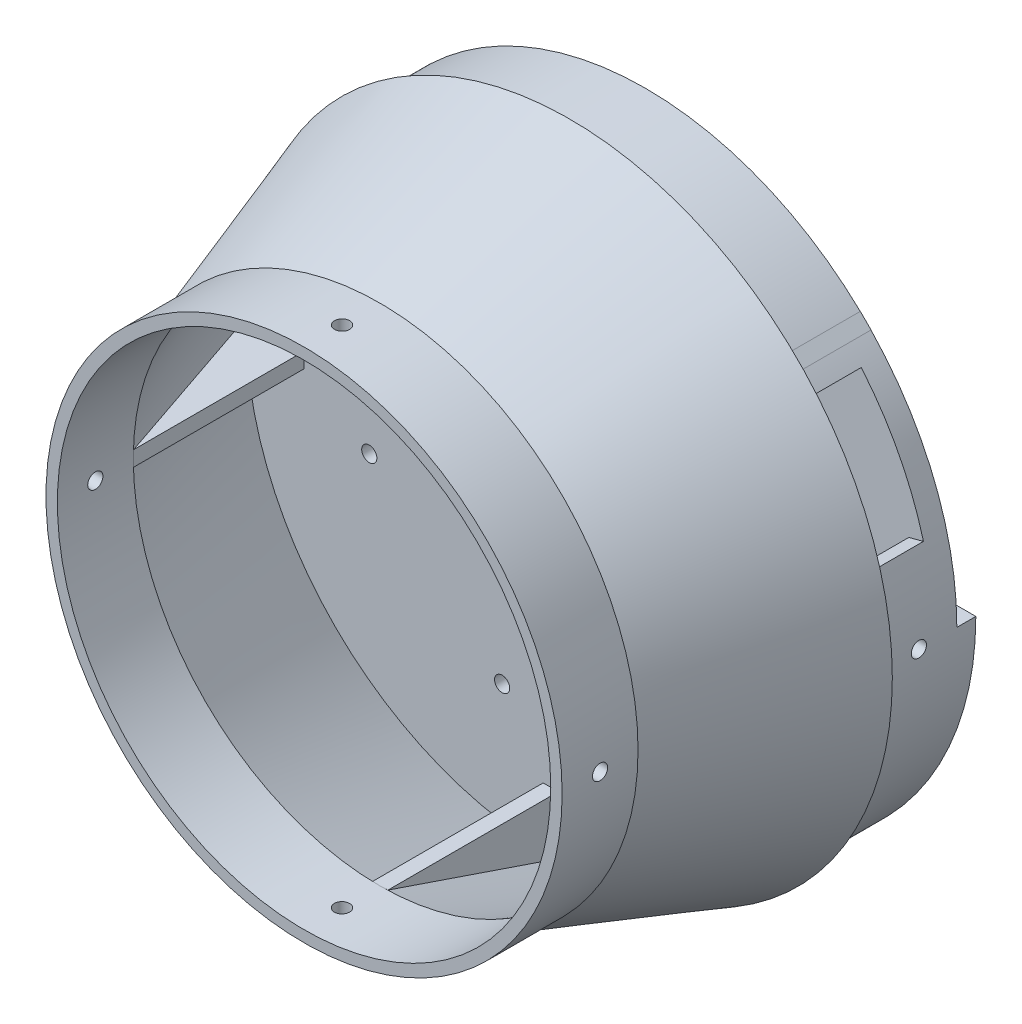
SolidWorks part; units mm, degrees
material "Polyetheretherketone (PEEK)"
ref_plane "Front Plane" through (0, 0, 0) normal (0, 0, 1) x (1, 0, 0)
ref_plane "Top Plane" through (0, 0, 0) normal (0, 1, 0) x (1, 0, 0)
ref_plane "Right Plane" through (0, 0, 0) normal (1, 0, 0) x (0, 0, -1)
sketch "Sketch10" plane through (0, 0, 0) normal (0, 1, 0) x (1, 0, 0)
  line L9 (68, 0) -> (85, 50)
  line L10 (65, 0) -> (65, -20)
  line L11 (65, -20) -> (68, -20)
  line L12 (68, -20) -> (68, 0)
  line L13 (85, 50) -> (0, 50)
  line L14 (0, 50) -> (0, 45)
  line L16 (0, 0) -> (0, 90.5218) construction
  line L17 (65, 0) -> (80.3, 45)
  line L18 (0, 45) -> (80.3, 45)
  dimension "D1" = 65
  dimension "D2" = 20
  dimension "D3" = 50
  dimension "D4" = 85
  dimension "D5" = 68
  dimension "D6" = 5
revolve "Revolve2" add sketch "Sketch10" angle 360 about L16
sketch "Sketch12" plane through (0, 0, 0) normal (0, 1, 0) x (1, 0, 0)
  line L4 (-80.3, 45) -> (-65, 0)
  line L5 (-65, 0) -> (-65, 45)
  line L6 (-80.3, 45) -> (80.3, 45) construction
  line L7 (-65, 45) -> (-80.3, 45)
extrude "Boss-Extrude5" add sketch "Sketch12" along normal blind 2 and the other way blind 2
pattern_circular "CirPattern3" count 4 every 90 about axis through (0, 0, -50) along (0, 0, 1) of "Boss-Extrude5"
sketch "Sketch13" plane through (0, 0, -50) normal (0, 0, -1) x (-1, 0, 0)
  arc A0 (70, 42.7083) -> (70, -42.7083) centre (0, 0) ccw
  arc A1 (70, 34.4093) -> (70, -34.4093) centre (0, 0) ccw
  circle A2 centre (0, 0) radius 82 construction
  circle A3 centre (0, 0) radius 78 construction
  circle A4 centre (0, 0) radius 82
  circle A5 centre (0, 0) radius 78
  dimension "D1" = 164
  dimension "D2" = 4
extrude "Boss-Extrude6" add sketch "Sketch13" along normal blind 20 contours A0 A4 A5 A1 region at (-76.7102, 21.5537, -50)
sketch "Sketch14" plane through (0, 0, 0) normal (0, 1, 0) x (1, 0, 0)
  line L0 (-65, -20) -> (65, -20) construction
  circle A0 centre (0, -10) radius 2
  dimension "D1" = 4
  dimension "D2" = 10
extrude "Cut-Extrude1" cut sketch "Sketch14" against normal blind 95
pattern_circular "CirPattern4" count 4 every 90 about axis through (0, 0, 20) along (0, 0, 1) of "Cut-Extrude1"
sketch "Sketch16" plane through (0, 0, 0) normal (0, 1, 0) x (1, 0, 0)
  line L0 (85, 50) -> (-85, 50) construction
  circle A0 centre (0, 60) radius 2
  dimension "D1" = 4
  dimension "D2" = 10
extrude "Cut-Extrude2" cut sketch "Sketch16" against normal blind 94
pattern_circular "CirPattern5" count 2 every 90 about axis through (0, 0, -70) along (0, 0, -1) of "Cut-Extrude2" other way count 2
sketch "Sketch17" plane through (0, 0, -50) normal (0, 0, -1) x (-1, 0, 0)
  line L0 (0, 0) -> (-47.8133, 12.8115) construction
  line L1 (0, 0) -> (-12.8115, 47.8133) construction
  circle A0 centre (-47.8133, 12.8115) radius 2
  circle A4 centre (-12.8115, 47.8133) radius 2
  circle A5 centre (12.8115, -47.8133) radius 2
  circle A6 centre (47.8133, -12.8115) radius 2
  point P12 (0, 0)
  point P16 (0, 0)
  dimension "D1" = 4
  dimension "D2" = 49.5
  dimension "D4" = 60
  dimension "D3" = 2
  dimension "D5" = 2
extrude "Cut-Extrude4" cut sketch "Sketch17" against normal blind 900
sketch "Sketch19" plane through (0, 0, -70) normal (0, 0, -1) x (-1, 0, 0)
  line L0 (0, 0) -> (0, 85) construction
  line L1 (0, 0) -> (-79.2059, 21.2232)
  line L6 (0, 0) -> (-62.8156, 52.7086)
  circle A0 centre (0, 0) radius 85 construction
  arc A2 (-62.8156, 52.7086) -> (-79.2059, 21.2232) centre (0, 0) ccw
  dimension "D1" = 75
  dimension "D2" = 50
extrude "Cut-Extrude7" cut sketch "Sketch19" against normal blind 20
mirror "Mirror1" about plane through (0, 0, 0) normal (1, 0, 0) of "Cut-Extrude7"
sketch "Sketch22" plane through (0, 0, -70) normal (0, 0, -1) x (-1, 0, 0)
  circle A2 centre (0, 0) radius 82
  circle A3 centre (0, 0) radius 60
  arc M2 (-59.7515, 50.1374) -> (59.7515, 50.1374) centre (0, 0) cw
  line M3 (59.7515, 50.1374) -> (62.8156, 52.7086)
  arc M4 (62.8156, 52.7086) -> (-62.8156, 52.7086) centre (0, 0) ccw
  line M5 (-62.8156, 52.7086) -> (-59.7515, 50.1374)
  dimension "D1" = 120
extrude "Boss-Extrude8" add sketch "Sketch22" against normal blind 6 contours A2 A3 M5 M3 M2 | M5 M2 M3 M4 region at (27.262, -74.9018, -70) region at (-60.4504, 52.4159, -70)
sketch "Sketch24" plane through (0, 0, -50) normal (0, 0, -1) x (-1, 0, 0)
  circle A0 centre (0, 0) radius 25
  dimension "D1" = 50
extrude "Cut-Extrude8" cut sketch "Sketch24" against normal blind 5
ref_plane "Plane1" through (0, 0, 0) normal (-0.7071, 0.7071, 0) x (0.7071, 0.7071, 0)
sketch "Sketch28" plane through (0, 0, 0) normal (-0.7071, 0.7071, 0) x (0.7071, 0.7071, 0)
  line L0 (-68, 50) -> (-68, 70)
  line L1 (82, 70) -> (-82, 70) construction
  line L2 (-68, 70) -> (-82, 70)
  line L3 (-82, 70) -> (-82, 50)
  line L4 (85, 50) -> (-85, 50) construction
  line L5 (-82, 70) -> (-82, 50) construction
  line L6 (-82, 50) -> (-68, 50)
extrude "Boss-Extrude9" add sketch "Sketch28" along normal blind 2 and the other way blind 2
pattern_circular "CirPattern6" count 4 every 90 about axis through (0, 0, -70) along (0, 0, -1) of "Boss-Extrude9"
sketch "Sketch29" plane through (0, 0, -70) normal (0, 0, -1) x (-1, 0, 0)
  line L6 (-75, 0) -> (-82, 0)
  line L8 (75, 0) -> (82, 0)
  arc A0 (-82, 0) -> (82, 0) centre (0, 0) ccw
  arc A2 (-75, 0) -> (75, 0) centre (0, 0) ccw
  dimension "D3" = 150
extrude "Boss-Extrude10" add sketch "Sketch29" along normal blind 5 contours A0 L8 A2 L6
sketch "Sketch30" plane through (0, 0, -50) normal (0, 0, -1) x (-1, 0, 0)
  line L3 (-53.6231, 44.9951) -> (-58.9854, 49.4946)
  line L5 (58.9854, 49.4946) -> (53.6231, 44.9951)
  line L6 (69.7336, 6.1009) -> (76.707, 6.711)
  line L7 (-69.4142, 9.0369) -> (-76.3556, 9.9406)
  line L10 (-69.4142, 9.0369) -> (-76.3556, 9.9406)
  line L12 (-53.6231, 44.9951) -> (-58.9854, 49.4946)
  line L13 (53.6231, 44.9951) -> (58.9854, 49.4946)
  line L14 (69.7336, 6.1009) -> (76.707, 6.711)
  arc A0 (-53.6231, 44.9951) -> (-69.4142, 9.0369) centre (0, 0) ccw
  arc A1 (69.7336, 6.1009) -> (53.6231, 44.9951) centre (0, 0) ccw
  arc A2 (-58.9854, 49.4946) -> (-76.3556, 9.9406) centre (0, 0) ccw
  arc A3 (76.707, 6.711) -> (58.9854, 49.4946) centre (0, 0) ccw
  dimension "D1" = 140
  dimension "D2" = 154
extrude "Cut-Extrude11" cut sketch "Sketch30" against normal blind 10 and the other way blind 10 contours L3 A2 L7 A0 region at (66.4437, 29.1789, -50)
extrude "Cut-Extrude12" cut sketch "Sketch30<5>" against normal blind 10 contours L6 A3 L5 A1 region at (-66.9048, 27.7129, -50)
sketch "Sketch30<5>" plane through (0, 0, -50) normal (0, 0, -1) x (-1, 0, 0) same geometry as "Sketch30"
sketch "Sketch31" plane through (0, 0, -50) normal (0, 0, -1) x (-1, 0, 0)
  line L0 (-75, 0) -> (-82, 0) construction
  line L1 (0, 0) -> (-54.5094, 16.6652)
  line L4 (-54.5094, 16.6652) -> (-38.2522, 11.6949)
  line L5 (-38.2522, 11.6949) -> (-54.5094, 16.6652)
  line L6 (-54.5094, 16.6652) -> (-62.0526, -8.0075)
  line L7 (-54.5094, 16.6652) -> (-38.2522, 11.6949)
  line L8 (-54.5094, 16.6652) -> (-55.3865, 13.7963)
  line L9 (-38.2522, 11.6949) -> (-39.1293, 8.826)
  line L10 (-55.3865, 13.7963) -> (-39.1293, 8.826)
  line L11 (-54.5094, 16.6652) -> (-49.7278, 15.2033)
  line L12 (-54.5094, 16.6652) -> (-52.4628, 23.3593)
  line L13 (-49.7278, 15.2033) -> (-47.6812, 21.8975)
  line L14 (-52.4628, 23.3593) -> (-47.6812, 21.8975)
  line L15 (-62.0526, -8.0075) -> (-41.9702, -14.1473)
  line L16 (-62.0526, -8.0075) -> (-62.9297, -10.8764)
  line L17 (-41.9702, -14.1473) -> (-42.8473, -17.0162)
  line L18 (-62.9297, -10.8764) -> (-42.8473, -17.0162)
  line L19 (-62.9297, -10.8764) -> (-58.1482, -12.3382)
  line L20 (-62.9297, -10.8764) -> (-64.9763, -17.5705)
  line L21 (-58.1482, -12.3382) -> (-60.1948, -19.0324)
  line L22 (-64.9763, -17.5705) -> (-60.1948, -19.0324)
  dimension "D2" = 17
  dimension "D5" = 17
  dimension "D6" = 25.8
  dimension "D7" = 3
  dimension "D8" = 5
  dimension "D9" = 21
  dimension "D10" = 3
  dimension "D11" = 7
  dimension "D12" = 5
  dimension "D13" = 7
extrude "Boss-Extrude11" add sketch "Sketch31" along normal blind 12 contours L14 L12 L7 L13 | L6 L10 L9 L1 L7 | L16 L18 L17 L15 | L20 L22 L21 L18 region at (46.8193, 12.7456, -50) region at (52.4499, -12.5118, -50) region at (51.0953, 19.2813, -50) region at (61.5622, -14.9544, -50)
sketch "Sketch32" plane through (54.5094, 16.6652, 0) normal (0.9563, 0.2924, 0) x (0, 0, -1)
  line L0 (50, -0.4) -> (56.2, -0.4) construction
  line L2 (50, -3) -> (50, 7) construction
  line L3 (56.2, -0.4) -> (56.2, -3) construction
  line L4 (62, -3) -> (50, -3) construction
  circle A0 centre (56.2, -0.4) radius 1.375
  dimension "D1" = 6.2
  dimension "D2" = 2.6
extrude "Cut-Extrude13" cut sketch "Sketch32" against normal blind 10
sketch "Sketch33" plane through (54.5094, 16.6652, 0) normal (0.9563, 0.2924, 0) x (0, 0, -1)
  line L0 (50, -28.4) -> (56.2, -28.4) construction
  line L1 (50, -71.4412) -> (50, -2.8618) construction
  line L2 (62, -25.8) -> (50, -25.8) construction
  circle A0 centre (56.2, -28.4) radius 1.375
  dimension "D1" = 6.2
  dimension "D2" = 2.6
extrude "Cut-Extrude14" cut sketch "Sketch33" against normal blind 10
mirror "Mirror2" about plane through (0, 0, 0) normal (1, 0, 0) of "Cut-Extrude13", "Boss-Extrude11", "Cut-Extrude14"
sketch "Sketch34" plane through (0, 0, -70) normal (0, 0, -1) x (-1, 0, 0)
  line L0 (0, 0) -> (0, 200)
  arc A0 (0, 200) -> (214.5955, 324.0552) centre (140.167, 205.1691) cw
  dimension "D1" = 200
